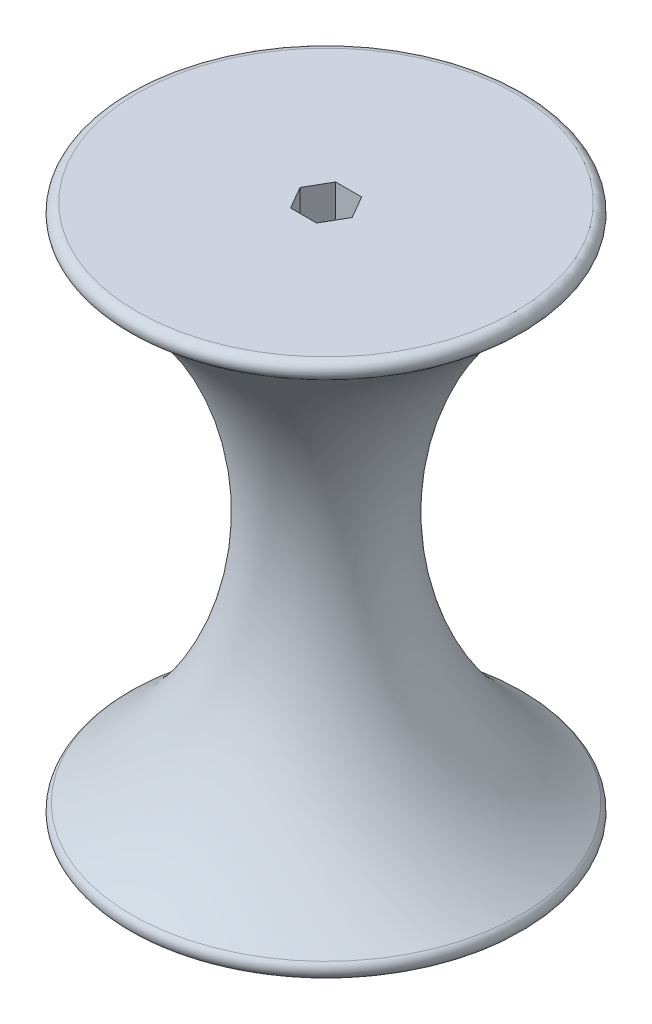
SolidWorks part; units mm, degrees
ref_plane "Front Plane" through (0, 0, 0) normal (0, 0, 1) x (1, 0, 0)
ref_plane "Top Plane" through (0, 0, 0) normal (0, 1, 0) x (1, 0, 0)
ref_plane "Right Plane" through (0, 0, 0) normal (1, 0, 0) x (0, 0, -1)
sketch "Sketch1" plane through (0, 0, 0) normal (0, 0, 1) x (1, 0, 0)
  line L1 (0, -76.2) -> (53.7699, -76.2)
  line L2 (0, -76.2) -> (0, 76.2)
  line L3 (0, 76.2) -> (53.7699, 76.2)
  arc A0 (55.2749, 71.6139) -> (55.2749, -71.6139) centre (107.95, 0) ccw
  arc A1 (55.2749, -71.6139) -> (53.7699, -76.2) centre (53.7699, -73.66) cw
  arc A2 (53.7699, 76.2) -> (55.2749, 71.6139) centre (53.7699, 73.66) cw
  point P10 (19.05, 0)
  point P12 (0, 0)
  dimension "D2" = 88.9
  dimension "D4" = 19.05
  dimension "D3" = 2.54
  dimension "D5" = 152.4
ref_axis "Axis1" through (0, -76.2, 0) along (0, 1, 0)
revolve "Revolve1" add sketch "Sketch1" angle 360 about axis through (0, -76.2, 0) along (0, 1, 0)
sketch "Sketch3" plane through (0, 76.2, 0) normal (0, 1, 0) x (1, 0, 0)
  line L0 (7.4057, 0) -> (3.7028, -6.4135)
  line L1 (3.7028, -6.4135) -> (-3.7028, -6.4135)
  line L2 (-3.7028, -6.4135) -> (-7.4057, 0)
  line L3 (-7.4057, 0) -> (-3.7028, 6.4135)
  line L4 (-3.7028, 6.4135) -> (3.7028, 6.4135)
  line L5 (3.7028, 6.4135) -> (7.4057, 0)
  line L6 (7.4057, 0) -> (-7.4057, 0) construction
  circle A1 centre (0, 0) radius 53.7699
  circle A3 centre (0, 0) radius 53.7699 construction
  point P5 (0, 0)
  dimension "D2" = 12.827
  dimension "D3" = 12.827
  dimension "D1" = 0
extrude "Cut-Extrude1" cut sketch "Sketch3" against normal through all
sketch "Sketch4" plane through (0, 76.2, 0) normal (0, 1, 0) x (1, 0, 0)
  line L0 (3.7028, 6.4135) -> (-3.7028, 6.4135) construction
  line L1 (3.7028, 6.4135) -> (-3.7028, 6.4135) construction
  line L2 (7.4057, 0) -> (56.3099, 0) construction
  line L3 (0, -6.4135) -> (0, 6.4135) construction
  line L4 (-3.7028, -6.4135) -> (3.7028, -6.4135) construction
  circle A0 centre (0, 0) radius 56.3099 construction
  circle A1 centre (0, 0) radius 56.3099 construction
ref_plane "Plane1" through (0, 0, -56.3035) normal (0, 0, 1) x (1, 0, 0)
ref_plane "Plane2" through (56.388, 0, 0) normal (1, 0, 0) x (0, 0, -1)
